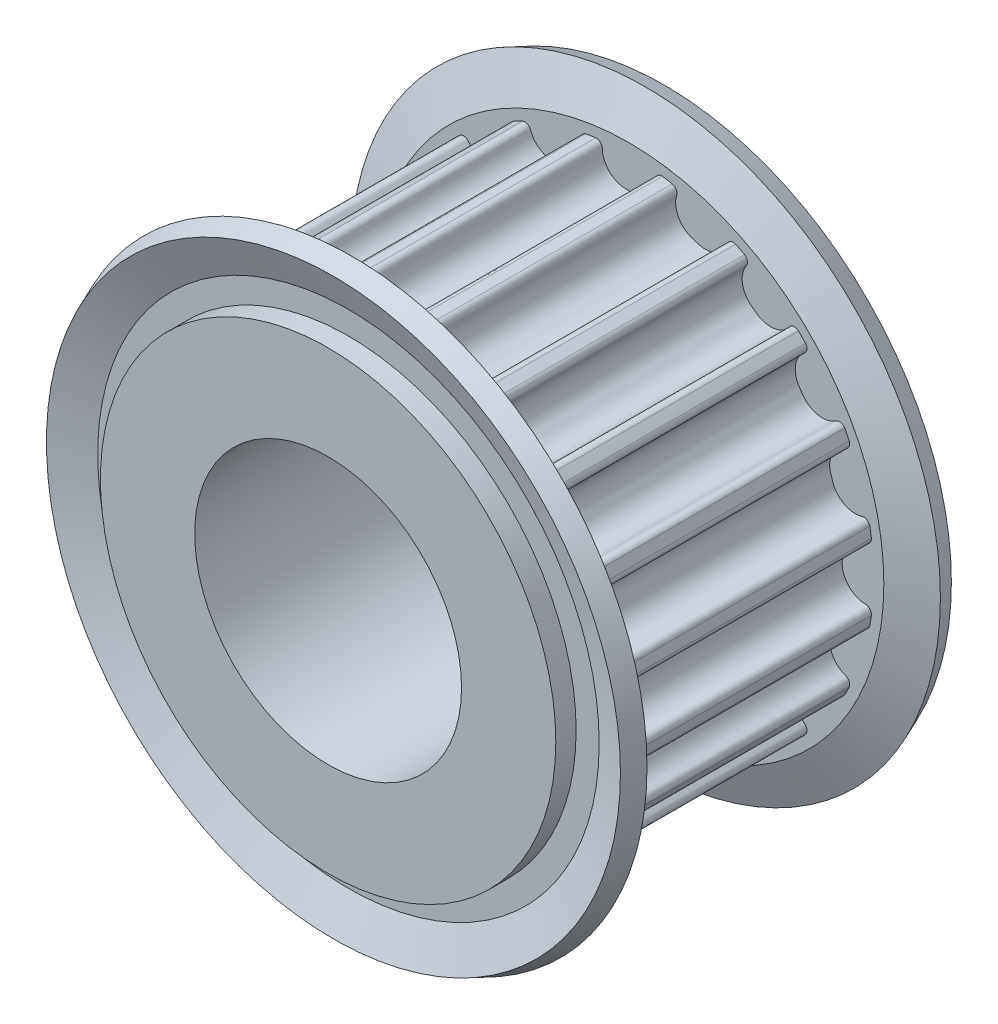
SolidWorks part; units mm, degrees
ref_plane "前视基准面" through (0, 0, 0) normal (0, 0, 1) x (1, 0, 0)
ref_plane "上视基准面" through (0, 0, 0) normal (0, 1, 0) x (1, 0, 0)
ref_plane "右视基准面" through (0, 0, 0) normal (1, 0, 0) x (0, 0, -1)
ref_axis "基准轴1" through (0, 0, 55) along (0, 0, -1)
sketch "SketchRevolveGearBelt01" plane through (0, 0, 0) normal (1, 0, 0) x (0, 0, -1)
  line L0 (0, 0) -> (1, 0) construction
  line L1 (6.4008, 0) -> (6.4008, 8.5326)
  line L2 (6.4008, 8.5326) -> (5.6388, 8.5326)
  line L3 (5.6388, 8.5326) -> (5.6388, 9.397)
  line L4 (5.6388, 9.397) -> (6.2015, 10.7556)
  line L5 (6.2015, 10.7556) -> (5.4975, 11.0472)
  line L6 (5.4975, 11.0472) -> (4.8768, 9.5486)
  line L7 (4.8768, 9.5486) -> (4.8768, 9.1676)
  line L8 (4.8768, 9.1676) -> (-4.8768, 9.1676)
  line L9 (-4.8768, 9.1676) -> (-4.8768, 9.5486)
  line L10 (-4.8768, 9.5486) -> (-5.4975, 11.0472)
  line L11 (-5.4975, 11.0472) -> (-6.2015, 10.7556)
  line L12 (-6.2015, 10.7556) -> (-5.6388, 9.397)
  line L13 (-5.6388, 9.397) -> (-5.6388, 8.5326)
  line L14 (-5.6388, 8.5326) -> (-6.4008, 8.5326)
  line L15 (-6.4008, 8.5326) -> (-6.4008, 0)
  line L16 (-6.4008, 0) -> (6.4008, 0)
  dimension "GearBeltFlange1OutsideLength" = 0.8644
  dimension "GearBeltFlange1X" = 0.5627
  dimension "GearBeltFlange1Y" = 1.3586
  dimension "GearBeltFlangeThickness" = 0.762
  dimension "GearBeltFlangeInside" = 0.381
  dimension "GearBeltOutsideDiameter" = 9.1676
  dimension "GearBeltFlange2X" = 0.5627
revolve "GearBelt01" add sketch "SketchRevolveGearBelt01" angle 360 about L0
sketch "SketchToothGearBelt01" plane through (0, 0, 0) normal (0, 0, 1) x (1, 0, 0)
  arc A0 (9.0809, 1.2614) -> (9.0809, -1.2614) centre (0, 0) cw
  spline S0 degree 3 poles (9.0809, -1.2614) (9.0827, -1.2485) (9.0837, -1.229) (9.0817, -1.203) (9.0786, -1.1837) (9.0738, -1.1647) (9.0675, -1.1462) (9.0596, -1.1283) (9.0502, -1.1112) (9.0393, -1.0949) (9.0272, -1.0796) (9.0137, -1.0654) (8.9991, -1.0524) (8.9835, -1.0407) (8.9669, -1.0303) (8.9495, -1.0215) (8.9314, -1.0141) (8.9127, -1.0083) (8.8936, -1.004) (8.8349, -0.9971) (8.7588, -0.996) (8.6681, -0.9767) (8.601, -0.9578) (8.5356, -0.9335) (8.4723, -0.9041) (8.4115, -0.8699) (8.3536, -0.8311) (8.2989, -0.7878) (8.2477, -0.7404) (8.2005, -0.6891) (8.1573, -0.6343) (8.1186, -0.5762) (8.0846, -0.5154) (8.0555, -0.452) (8.0314, -0.3865) (8.0124, -0.3194) (7.9989, -0.251) (7.9906, -0.1817) (7.9885, -0.1166) (7.989, -0.056) (7.9888, 0) (7.989, 0.056) (7.9885, 0.1166) (7.9906, 0.1817) (7.9989, 0.251) (8.0124, 0.3194) (8.0314, 0.3865) (8.0555, 0.452) (8.0846, 0.5154) (8.1186, 0.5762) (8.1573, 0.6343) (8.2005, 0.6891) (8.2477, 0.7404) (8.2989, 0.7878) (8.3536, 0.8311) (8.4115, 0.8699) (8.4723, 0.9041) (8.5356, 0.9335) (8.601, 0.9578) (8.6681, 0.9767) (8.7588, 0.996) (8.8349, 0.9971) (8.8936, 1.004) (8.9127, 1.0083) (8.9314, 1.0141) (8.9495, 1.0215) (8.9669, 1.0303) (8.9835, 1.0407) (8.9991, 1.0524) (9.0137, 1.0654) (9.0272, 1.0796) (9.0393, 1.0949) (9.0502, 1.1112) (9.0596, 1.1283) (9.0675, 1.1462) (9.0738, 1.1647) (9.0786, 1.1837) (9.0817, 1.203) (9.0837, 1.229) (9.0827, 1.2485) (9.0809, 1.2614) knots 0 0 0 0 0.010413 0.01562 0.020826 0.026033 0.031239 0.036446 0.041652 0.046859 0.052065 0.057272 0.062478 0.067685 0.072891 0.078098 0.083304 0.088511 0.093717 0.098924 0.135739 0.154317 0.172895 0.191472 0.21005 0.228628 0.247206 0.265784 0.284362 0.302939 0.321517 0.340095 0.358673 0.377251 0.395829 0.414406 0.432984 0.451562 0.47014 0.48507 0.5 0.51493 0.52986 0.548438 0.567016 0.585594 0.604171 0.622749 0.641327 0.659905 0.678483 0.697061 0.715638 0.734216 0.752794 0.771372 0.78995 0.808528 0.827105 0.845683 0.864261 0.901076 0.906283 0.911489 0.916696 0.921902 0.927109 0.932315 0.937522 0.942728 0.947935 0.953141 0.958348 0.963554 0.968761 0.973967 0.979174 0.98438 0.989587 1 1 1 1
extrude "ToothExtrudeCutGearBelt01" cut sketch "SketchToothGearBelt01" against normal blind 4.8768 and the other way blind 4.8768
pattern_circular "PatternGearBelt01" count 20 every 18 about axis through (0, 0, 55) along (0, 0, -1) of "ToothExtrudeCutGearBelt01"
sketch "BoreRevolveSketch" plane through (0, 0, 0) normal (1, 0, 0) x (0, 0, -1)
  line L0 (0, 0) -> (1, 0) construction
  line L1 (-6.4008, 0) -> (6.4008, 0)
  line L2 (6.4008, 0) -> (6.4008, 5)
  line L3 (6.4008, 5) -> (-6.4008, 5)
  line L4 (-6.4008, 5) -> (-6.4008, 0)
  dimension "TaperSide1" = 5
  dimension "TaperSide2" = 5
revolve "BoreRevolveCut" cut sketch "BoreRevolveSketch" angle 360 about L0
sketch "AuxiliarySketchGearBelt01" plane through (0, 0, 0) normal (0, 0, 1) x (1, 0, 0)
  circle A0 centre (0, 0) radius 9.5486 construction
  dimension "PitchDiameter" = 19.0972
